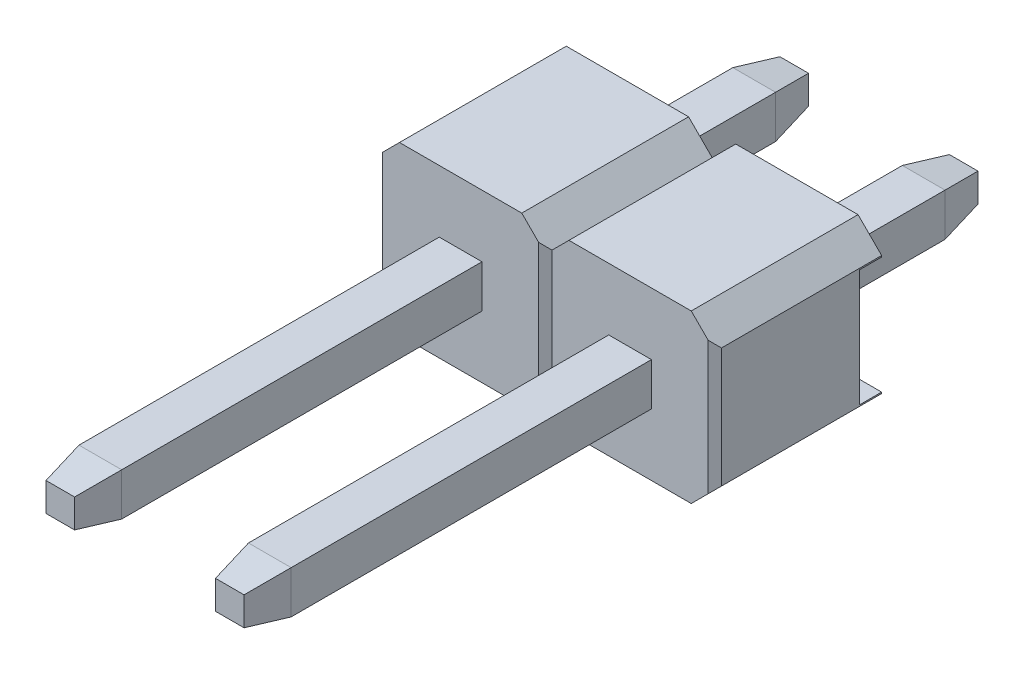
SolidWorks part; units mm, degrees
ref_plane "Front Plane" through (0, 0, 0) normal (0, 0, 1) x (1, 0, 0)
ref_plane "Top Plane" through (0, 0, 0) normal (0, 1, 0) x (1, 0, 0)
ref_plane "Right Plane" through (0, 0, 0) normal (1, 0, 0) x (0, 0, -1)
sketch "Sketch1" plane through (0, 0, 0) normal (0, 0, 1) x (1, 0, 0)
  line L0 (-1.27, 0.8964) -> (-0.9164, 1.25)
  line L1 (-0.9164, 1.25) -> (0.9164, 1.25)
  line L2 (-1.27, 0.8964) -> (-1.27, -0.8964)
  line L3 (-0.9164, -1.25) -> (0.9164, -1.25)
  line L4 (1.27, 0.8964) -> (1.27, -0.8964)
  line L5 (-1.27, -0.8964) -> (-0.9164, -1.25)
  line L6 (0.9164, -1.25) -> (1.27, -0.8964)
  line L7 (1.27, 0.8964) -> (0.9164, 1.25)
  point P0 (1.27, -1.25)
  point P7 (-1.27, 1.25)
  point P10 (-1.27, -1.25)
  point P15 (1.27, 1.25)
  dimension "D5" = 0.25
  dimension "D1" = 2.54
  dimension "D2" = 2.5
  dimension "D3" = 1.27
  dimension "D4" = 1.25
  dimension "D6" = 0.25
  dimension "D7" = 0.25
  dimension "D8" = 0.25
extrude "Extrude1" add sketch "Sketch1" along normal blind 1.25 and the other way blind 1.25
sketch "Sketch4" plane through (0, 0, 0) normal (0, 1, 0) x (1, 0, 0)
  line L0 (-1.27, -1.15) -> (-1.17, -1.25)
  line L1 (-1.17, -1.25) -> (-1.27, -1.25)
  line L2 (-1.27, -1.25) -> (-1.27, -1.15)
  line L3 (1.17, -1.25) -> (1.27, -1.15)
  line L4 (1.27, -1.15) -> (1.27, -1.25)
  line L5 (1.27, -1.25) -> (1.17, -1.25)
extrude "Cut-Extrude3" cut sketch "Sketch4" against normal through all and the other way through all
pattern_linear "LPattern4" count 2 spacing 2.54 along (-1, 0, 0) of "Extrude1", "Cut-Extrude3"
sketch "Sketch2" plane through (0, 0, 0) normal (1, 0, 0) x (0, -1, 0)
  line L1 (-0.8764, 1.25) -> (0.8764, 1.25)
  line L2 (-0.8764, 1.25) -> (-0.8764, 0.92)
  line L3 (-0.8764, 0.92) -> (0.8764, 0.92)
  line L4 (0.8764, 1.25) -> (0.8764, 0.92)
  dimension "D1" = 0.33
extrude "Cut-Extrude1" cut sketch "Sketch2" against normal through all and the other way through all
sketch "Sketch3" plane through (0, 0, 0) normal (1, 0, 0) x (0, 0, -1)
  line L0 (-7.25, 0) -> (3.75, 0)
  line L1 (1.25, 1.25) -> (1.25, 0.8964) construction
  dimension "D1" = 6
  dimension "D2" = 2.5
extrude "Extrude-Thin1" add sketch "Sketch3" along normal blind 0.32 and the other way blind 0.32 thin thin type mid plane wall 0.64
pattern_linear "LPattern5" count 1 spacing 2.54 along (1, 0, 0) count 2 spacing 2.54 along (-1, 0, 0) of "Extrude-Thin1"
chamfer "Chamfer2" distance 0.6 angle 10 16 edges at (0.32, 0, 7.25) (0, -0.32, 7.25) (-0.32, 0, 7.25) (0, 0.32, 7.25) (0.32, 0, -3.75) (-0.32, 0, -3.75) (-2.22, 0, -3.75) (-2.86, 0, -3.75) (-2.22, 0, 7.25) (-2.54, -0.32, 7.25) (-2.86, 0, 7.25) (-2.54, 0.32, 7.25) (-2.54, 0.32, -3.75) (-2.54, -0.32, -3.75) (0, 0.32, -3.75) (0, -0.32, -3.75) first distance on face at (0.32, 0, 4.25) first distance on face at (0, -0.32, 4.25) first distance on face at (-0.32, 0, 4.25) first distance on face at (0, 0.32, 4.25) first distance on face at (0.32, 0, -2.335) first distance on face at (-0.32, 0, -2.335) first distance on face at (-2.22, 0, -2.335) first distance on face at (-2.86, 0, -2.335) first distance on face at (-2.22, 0, 4.25) first distance on face at (-2.54, -0.32, 4.25) first distance on face at (-2.86, 0, 4.25) first distance on face at (-2.54, 0.32, 4.25) first distance on face at (-2.54, 0.32, -2.335) first distance on face at (-2.54, -0.32, -2.335) first distance on face at (0, 0.32, -2.335) first distance on face at (0, -0.32, -2.335)
ref_plane "Board Plane" through (0, 0, -1.5) normal (0, 0, 1) x (1, 0, 0)
sketch "Component_Outline" plane through (0, 0, -1.5) normal (0, 0, 1) x (1, 0, 0)
  line L0 (0.9164, 1.25) -> (1.27, 0.8964)
  line L1 (1.27, 0.8964) -> (1.27, -0.8964)
  line L2 (1.27, -0.8964) -> (0.9164, -1.25)
  line L3 (0.9164, -1.25) -> (-0.9164, -1.25)
  line L4 (-0.9164, -1.25) -> (-1.27, -0.8964)
  line L5 (-1.27, -0.8964) -> (-1.6236, -1.25)
  line L6 (-1.6236, -1.25) -> (-3.4564, -1.25)
  line L7 (-3.4564, -1.25) -> (-3.81, -0.8964)
  line L8 (-3.81, -0.8964) -> (-3.81, 0.8964)
  line L9 (-3.81, 0.8964) -> (-3.4564, 1.25)
  line L10 (-3.4564, 1.25) -> (-1.6236, 1.25)
  line L11 (-1.6236, 1.25) -> (-1.27, 0.8964)
  line L12 (-1.27, 0.8964) -> (-0.9164, 1.25)
  line L13 (-0.9164, 1.25) -> (0.9164, 1.25)
  point P20 (0, 0)
